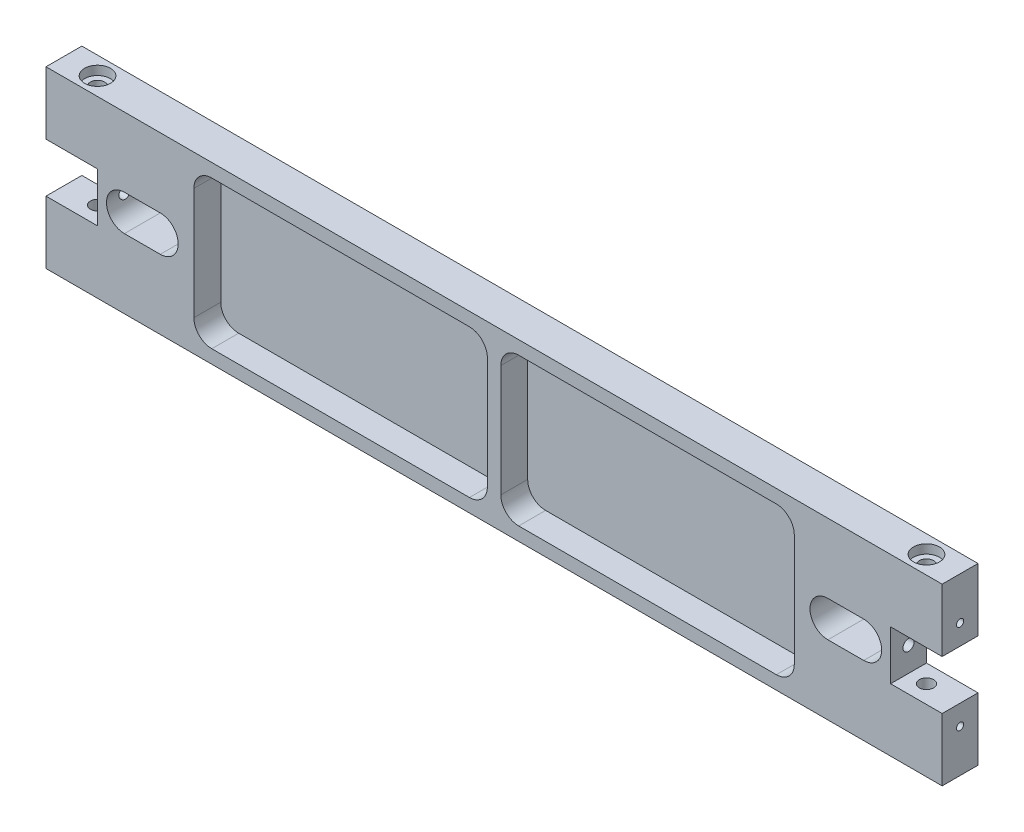
SolidWorks part; units mm, degrees
material "POM Acetalkopolymer"
ref_plane "Ebene vorne" through (0, 0, 0) normal (0, 0, 1) x (1, 0, 0)
ref_plane "Ebene oben" through (0, 0, 0) normal (0, 1, 0) x (1, 0, 0)
ref_plane "Ebene rechts" through (0, 0, 0) normal (1, 0, 0) x (0, 0, -1)
sketch "Skizze2" plane through (0, 0, 0) normal (0, 0, -1) x (1, 0, 0)
  line L0 (0, 33.696) -> (0, 0) construction
  line L2 (-100, 19.5) -> (-100, 5.5)
  line L4 (-100, 5.5) -> (-88.5, 5.5)
  line L5 (-88.5, 5.5) -> (-88.5, 0)
  line L6 (-100, 19.5) -> (0, 19.5)
  line L7 (0, 19.5) -> (0, 0)
  line L8 (-88.5, 0) -> (0, 0) construction
  line L9 (-88.5, 0) -> (0, 0)
  dimension "D1" = 177
  dimension "D2" = 11
  dimension "D3" = 200
  dimension "D5" = 39
extrude "Aufsatz-Linear austragen1" add sketch "Skizze2" along normal mid plane 8
hole_wizard "Stirnsenkung für  M3 Zylinderschraube mit Schlitz/Kreuzschlitz1" positions "Skizze7" profile "Skizze8" counterbore size "M3" standard "DIN" end condition through all
sketch "Skizze7" plane through (0, -19.5, 0) normal (0, -1, 0) x (-1, 0, 0)
  line L0 (100, 0) -> (92.5, 0)
  line L1 (100, 4) -> (100, -4) construction
  point P0 (92.5, 0)
  dimension "D1" = 7.5
sketch "Skizze8" plane through (-92.5, -19.5, 0) normal (1, 0, 0) x (0, 0, -1)
  line L0 (0, 0) -> (0, 19.5)
  line L1 (0, 19.5) -> (1.6, 19.5)
  line L3 (1.6, 19.5) -> (1.6, 2)
  line L4 (1.6, 2) -> (2.9, 2)
  line L5 (2.9, 2) -> (2.9, 0)
  line L7 (2.9, 0) -> (0, 0)
  line L11 (0, -6.35) -> (0, 107.95) construction
  dimension "Bohrerdurchmesser" = 3.2
  dimension "Bohrungstiefe" = 19.5
  dimension "Senkdurchmesser2" = 5.8
  dimension "Senktiefe2" = 2
mirror "Spiegeln2" about plane through (0, 0, 0) normal (0, 1, 0) of bodies 110 101
hole_wizard "M3 Gewindebohrung1" positions "Skizze10" profile "Skizze9" tap size "M3" standard "DIN"
sketch "Skizze10" plane through (-88.5, 0, 0) normal (-1, 0, 0) x (0, 0, 1)
  point P0 (0, 0)
sketch "Skizze9" plane through (-88.5, 0, 0) normal (0, 1, 0) x (0, 0, 1)
  line L0 (0, 0) -> (0, 9.2511)
  line L1 (0, 9.2511) -> (1.25, 8.5)
  line L2 (1.25, 8.5) -> (1.25, 0)
  line L5 (1.25, 0) -> (0, 0)
  line L10 (0, 9.2511) -> (-1.25, 8.5) construction
  line L11 (0, -6.35) -> (0, 107.95) construction
  dimension "Bohrerdurchmesser" = 2.5
  dimension "Bohrungstiefe" = 8.5
  dimension "Spitzenwinkel" = 118
cosmetic thread "Bohrungsgewinde4" parameters "D1"=6, "D2"=3
hole_wizard "M2 Gewindebohrung1" positions "Skizze12" profile "Skizze11" tap size "M2" standard "DIN"
sketch "Skizze12" plane through (-100, 0, 0) normal (-1, 0, 0) x (0, 0, 1)
  line L0 (0, -10) -> (0, 10) construction
  point P0 (0, 10)
  point P2 (0, -10)
  dimension "D1" = 20
sketch "Skizze11" plane through (-100, 10, 0) normal (0, 1, 0) x (0, 0, 1)
  line L0 (0, 0) -> (0, 6.4807)
  line L1 (0, 6.4807) -> (0.8, 6)
  line L2 (0.8, 6) -> (0.8, 0)
  line L5 (0.8, 0) -> (0, 0)
  line L10 (0, 6.4807) -> (-0.8, 6) construction
  line L11 (0, -6.35) -> (0, 107.95) construction
  dimension "Bohrerdurchmesser" = 1.6
  dimension "Bohrungstiefe" = 6
  dimension "Spitzenwinkel" = 118
cosmetic thread "Bohrungsgewinde2" parameters "D1"=4, "D2"=2
cosmetic thread "Bohrungsgewinde3" parameters "D1"=4, "D2"=2
mirror "Spiegeln3" about plane through (0, 0, 0) normal (1, 0, 0) of bodies 112 103
sketch "Skizze3" plane through (0, 0, 4) normal (0, 0, 1) x (1, 0, 0)
  line L0 (-1.5, 0) -> (1.5, 0) construction
  line L1 (-67, 16.5) -> (-1.5, 16.5)
  line L2 (-67, 16.5) -> (-67, -16.5)
  line L3 (-67, -16.5) -> (-1.5, -16.5)
  line L4 (-1.5, 16.5) -> (-1.5, -16.5)
  line L5 (1.5, 16.5) -> (67, 16.5)
  line L6 (1.5, 16.5) -> (1.5, -16.5)
  line L7 (-82.5, 0) -> (-74.5, 0) construction
  line L8 (-82.5, 4) -> (-74.5, 4)
  line L9 (-82.5, -4) -> (-74.5, -4)
  line L10 (74.5, 0) -> (82.5, 0) construction
  line L11 (74.5, 4) -> (82.5, 4)
  line L12 (74.5, -4) -> (82.5, -4)
  line L14 (1.5, -16.5) -> (67, -16.5)
  line L15 (67, 16.5) -> (67, -16.5)
  line L16 (100, 19.5) -> (-100, 19.5) construction
  line L18 (-92.5, 23.2298) -> (-92.5, -23.108) construction
  line L19 (-88.5, -5.5) -> (-88.5, 5.5) construction
  line L20 (0, 19.5) -> (0, -19.5) construction
  line L21 (100, -19.5) -> (-100, -19.5) construction
  arc A4 (-82.5, 4) -> (-82.5, -4) centre (-82.5, 0) ccw
  arc A5 (-74.5, -4) -> (-74.5, 4) centre (-74.5, 0) ccw
  arc A6 (74.5, 4) -> (74.5, -4) centre (74.5, 0) ccw
  arc A7 (82.5, -4) -> (82.5, 4) centre (82.5, 0) ccw
  point P19 (-78.5, 0)
  point P24 (78.5, 0)
  dimension "D4" = 8
  dimension "D1" = 3
  dimension "D2" = 3
  dimension "D3" = 14
  dimension "D5" = 8
  dimension "D6" = 4
  dimension "D7" = 67
extrude "Schnitt-Linear austragen1" cut sketch "Skizze3" against normal offset from surface (6 mm away) 2 contours L4 L1 L2 L3 | L15 L5 L6 L14 region at (-34.25, 0, 4) region at (34.25, 0, 4) up to face at (0, 0, -4)
extrude "Schnitt-Linear austragen2" cut sketch "Skizze3<3>" against normal through all contours L9 A5 L8 A4 | L12 A7 L11 A6 region at (-78.5, 0, 4) region at (78.5, 0, 4)
sketch "Skizze3<3>" plane through (0, 0, 4) normal (0, 0, 1) x (1, 0, 0) same geometry as "Skizze3"
fillet "Verrundung1" radius 4 8 edges at (67, -16.5, 1) (67, 16.5, 1) (-1.5, 16.5, 1) (1.5, 16.5, 1) (1.5, -16.5, 1) (-1.5, -16.5, 1) (-67, -16.5, 1) (-67, 16.5, 1)
sketch "Skizze13" [suppressed] plane through (0, 0, 4) normal (0, 0, 1) x (1, 0, 0)
  line L1 (-88.5, 5.5) -> (-100, 5.5)
  line L2 (-88.5, 5.5) -> (-88.5, -5.5)
  line L3 (-88.5, -5.5) -> (-100, -5.5)
  line L4 (-100, 5.5) -> (-100, -5.5)
  line L5 (88.5, 5.5) -> (100, 5.5)
  line L6 (88.5, 5.5) -> (88.5, -5.5)
  line L7 (88.5, -5.5) -> (100, -5.5)
  line L8 (100, 5.5) -> (100, -5.5)
extrude "Aufsatz-Linear austragen2" [suppressed] add sketch "Skizze13" against normal up to surface (8 mm away)
